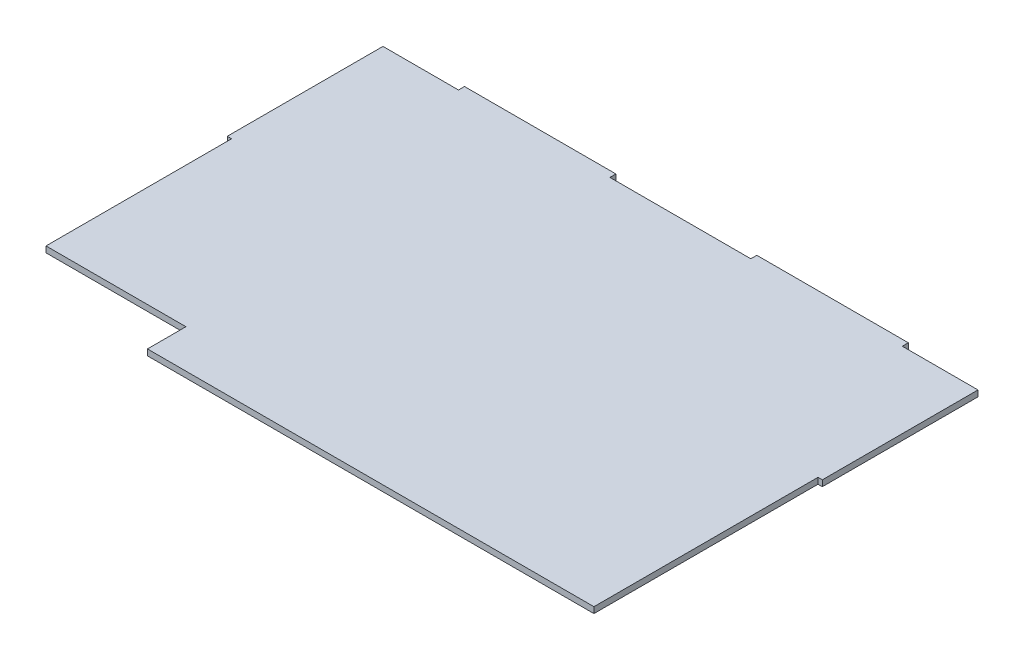
SolidWorks part; units mm, degrees
material "6061-T6 (SS)"
ref_plane "X-Y Datum" through (0, 0, 0) normal (0, 0, 1) x (1, 0, 0)
ref_plane "X-Z Datum" through (0, 0, 0) normal (0, 1, 0) x (1, 0, 0)
ref_plane "Y-Z Datum" through (0, 0, 0) normal (1, 0, 0) x (0, 0, -1)
sketch "Sketch1" plane through (0, 0, 0) normal (0, 0, 1) x (1, 0, 0)
  line L1 (-157.1648, -1.5875) -> (157.1648, -1.5875)
  line L2 (-157.1648, -1.5875) -> (-157.1648, 1.5875)
  line L3 (-157.1648, 1.5875) -> (157.1648, 1.5875)
  line L4 (157.1648, -1.5875) -> (157.1648, 1.5875)
  line L5 (-157.1648, -1.5875) -> (157.1648, 1.5875) construction
  line L6 (-157.1648, 1.5875) -> (157.1648, -1.5875) construction
  point P0 (0, 0)
  dimension "D1" = 314.3296
  dimension "D2" = 3.175
extrude "Boss-Extrude1" add sketch "Sketch1" along normal blind 200.6
sketch "Sketch3" plane through (0, 0, 0) normal (0, 0, -1) x (-1, 0, 0)
  line L0 (-157.1648, 0) -> (-77.1648, 0) construction
  line L1 (-157.1648, -1.5875) -> (-157.1648, 1.5875) construction
  line L2 (-157.1648, 1.5875) -> (157.1648, 1.5875) construction
  line L3 (-117.1648, -1.5875) -> (-37.1648, -1.5875)
  line L4 (-117.1648, -1.5875) -> (-117.1648, 1.5875)
  line L5 (-117.1648, 1.5875) -> (-37.1648, 1.5875)
  line L6 (-37.1648, -1.5875) -> (-37.1648, 1.5875)
  line L7 (-117.1648, -1.5875) -> (-37.1648, 1.5875) construction
  line L8 (-117.1648, 1.5875) -> (-37.1648, -1.5875) construction
  line L14 (-157.1648, 1.5875) -> (-117.1648, 1.5875)
  line L15 (-157.1648, 1.5875) -> (-157.1648, -1.5875)
  line L16 (-157.1648, -1.5875) -> (-117.1648, -1.5875)
  line L17 (-117.1648, 1.5875) -> (-117.1648, -1.5875)
  line L19 (-37.1648, 1.5875) -> (-37.1648, -1.5875)
  line M3 (-157.1648, -1.5875) -> (157.1648, -1.5875)
  line M5 (157.1648, 1.5875) -> (-157.1648, 1.5875)
  dimension "D1" = 40
  dimension "D2" = 80
sketch "Sketch5" plane through (0, 1.5875, 0) normal (0, 1, 0) x (1, 0, 0)
  line L1 (-157.1648, -200.6) -> (-154.8788, -200.6)
  line L3 (-157.1648, -200.6) -> (-157.1648, -82.236)
  line L5 (-157.1648, -82.236) -> (-154.8788, -82.236)
  line L6 (-154.8788, -200.6) -> (-154.8788, -82.236)
  line M11 (-157.1648, 0) -> (-157.1648, -200.6)
  line M12 (-157.1648, -200.6) -> (157.1648, -200.6)
  dimension "D1" = 118.364
  dimension "D2" = 2.286
extrude "Cut-Extrude2" cut sketch "Sketch5" against normal blind 3.175 and the other way through all contours M12 M11 region at (-156.0218, 1.5875, 141.418)
mirror "Mirror1" about plane through (0, 0, 0) normal (1, 0, 0) of "Cut-Extrude2"
sketch "Sketch6" plane through (0, 1.5875, 0) normal (0, 1, 0) x (1, 0, 0)
  line L6 (-157.1648, -180.28) -> (-80.9648, -180.28)
  line L7 (-157.1648, -180.28) -> (-157.1648, -200.6)
  line L8 (-157.1648, -200.6) -> (-80.9648, -200.6)
  line L9 (-80.9648, -180.28) -> (-80.9648, -200.6)
  line L10 (154.8788, -200.6) -> (-154.8788, -200.6) construction
  line L11 (-157.1648, -82.236) -> (-157.1648, 0) construction
  line L13 (154.8788, -200.6) -> (-80.9648, -200.6)
  line L14 (154.8788, -200.6) -> (154.8788, -180.28)
  line L15 (154.8788, -180.28) -> (-80.9648, -180.28)
  line L16 (-80.9648, -200.6) -> (-80.9648, -180.28)
  line M18 (-154.8788, -82.236) -> (-154.8788, -200.6)
  line M19 (-154.8788, -200.6) -> (154.8788, -200.6)
  dimension "D1" = 76.2
  dimension "D2" = 20.32
extrude "Cut-Extrude4" cut sketch "Sketch6" against normal through all contours L9 L6 M18 M19 region at (-117.9218, 1.5875, 190.44)
sketch "Sketch7" [suppressed] plane through (0, 1.5875, 0) normal (0, 1, 0) x (1, 0, 0)
  line L1 (-81.2823, -215.455) -> (155.1963, -215.455)
  line L2 (-81.2823, -215.455) -> (-81.2823, -235.775)
  line L3 (-81.2823, -235.775) -> (155.1963, -235.775)
  line L4 (155.1963, -215.455) -> (155.1963, -235.775)
extrude "Cut-Extrude5" [suppressed] cut sketch "Sketch7" against normal through all
sketch "Sketch8" plane through (0, 1.5875, 0) normal (0, 1, 0) x (1, 0, 0)
  line L0 (154.8788, -200.6) -> (-80.9648, -200.6) construction
  line L1 (157.1648, -180.28) -> (80.9648, -180.28)
  line L2 (157.1648, -180.28) -> (157.1648, -200.6)
  line L3 (157.1648, -200.6) -> (80.9648, -200.6)
  line L4 (80.9648, -180.28) -> (80.9648, -200.6)
  line L5 (157.1648, -82.236) -> (157.1648, 0) construction
  dimension "D1" = 20.32
  dimension "D2" = 76.2
extrude "Cut-Extrude6" [suppressed] cut sketch "Sketch8" against normal through all
sketch "Sketch9" [suppressed] plane through (0, 0, 215.455) normal (0, 0, 1) x (1, 0, 0)
  line L4 (155.1963, 1.5875) -> (-155.1963, 1.5875)
  line L5 (-155.1963, 1.5875) -> (-155.1963, -1.5875)
  line L6 (-155.1963, -1.5875) -> (155.1963, -1.5875)
  line L7 (155.1963, -1.5875) -> (155.1963, 1.5875)
  line L8 (155.1963, 1.5875) -> (-155.1963, 1.5875)
  line L9 (-155.1963, 1.5875) -> (-155.1963, -1.5875)
  line L10 (-155.1963, -1.5875) -> (155.1963, -1.5875)
  line L11 (155.1963, -1.5875) -> (155.1963, 1.5875)
  dimension "D1" = 0
extrude "Cut-Extrude7" [suppressed] cut sketch "Sketch9" against normal blind 11.68
extrude "Boss-Extrude2" [suppressed] add sketch "Sketch3" along normal blind 3.175 contours L6 L4 M3 M5
pattern_linear "LPattern2" [suppressed] count 2 spacing 154.43 of bodies 116
sketch "Sketch10" [suppressed] plane through (0, -1.5875, 0) normal (0, -1, 0) x (1, 0, 0)
  line L8 (157.1648, 0) -> (195.2648, 0)
  line L9 (195.2648, 0) -> (157.1648, 50.8)
  line L10 (157.1648, 82.236) -> (157.1648, 0) construction
  line L11 (157.1648, 50.8) -> (157.1648, 0)
  dimension "D1" = 50.8
  dimension "D2" = 38.1
extrude "Boss-Extrude3" [suppressed] add sketch "Sketch10" against normal blind 3.175
sketch "Sketch11" plane through (0, 0, 0) normal (0, 0, -1) x (-1, 0, 0)
  line L1 (37.2652, -1.5875) -> (117.2652, -1.5875)
  line L2 (37.2652, -1.5875) -> (37.2652, 1.5875)
  line L3 (37.2652, 1.5875) -> (117.2652, 1.5875)
  line L4 (117.2652, -1.5875) -> (117.2652, 1.5875)
  line L5 (-117.1668, -1.5875) -> (-37.1668, -1.5875)
  line L6 (-117.1668, -1.5875) -> (-117.1668, 1.5875)
  line L7 (-117.1668, 1.5875) -> (-37.1668, 1.5875)
  line L8 (-37.1668, -1.5875) -> (-37.1668, 1.5875)
extrude "Boss-Extrude4" add sketch "Sketch11" along normal blind 3.175
